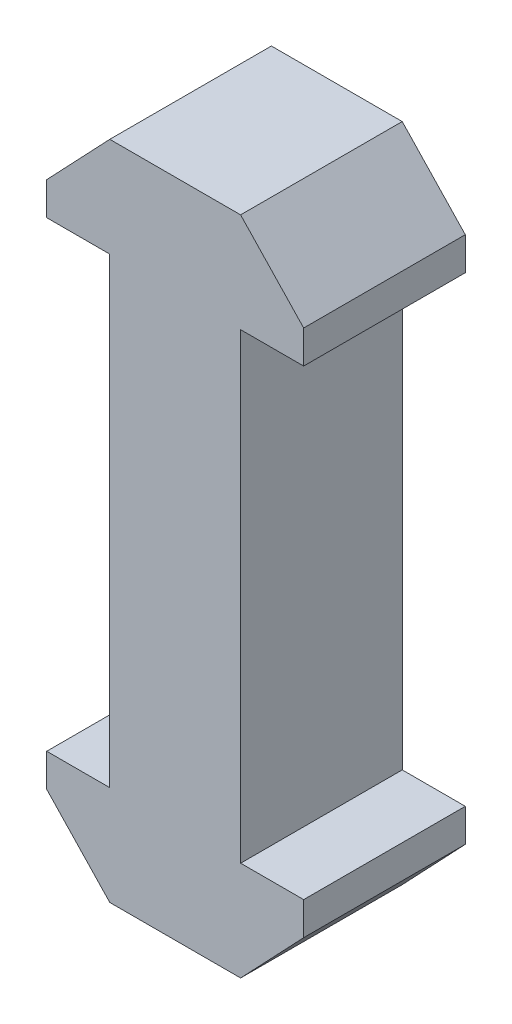
SolidWorks part; units mm, degrees
ref_plane "Front Plane" through (0, 0, 0) normal (0, 0, 1) x (1, 0, 0)
ref_plane "Top Plane" through (0, 0, 0) normal (0, 1, 0) x (1, 0, 0)
ref_plane "Right Plane" through (0, 0, 0) normal (1, 0, 0) x (0, 0, -1)
sketch "Sketch1" plane through (0, 0, 0) normal (0, 0, 1) x (1, 0, 0)
  line L3 (0, 0) -> (0, 14.2953) construction
  line L8 (0, 14.2953) -> (-8.6643, 14.2953) construction
  line L14 (-4.05, 0) -> (-4.05, 28.5906)
  line L15 (4.05, 0) -> (4.05, 28.5906)
  point P5 (-4.05, 14.2953)
  point P6 (4.05, 14.2953)
  line B0 (7.95, 0) -> (7.95, -2.04)
  line B1 (4.048, -6.1524) -> (-4.048, -6.1524)
  line B2 (-7.95, -2.04) -> (-7.95, 0)
  line B3 (-7.95, 0) -> (7.95, 0)
  line B4 (7.95, -2.04) -> (4.048, -6.1524)
  line B5 (-4.048, -6.1524) -> (-7.95, -2.04)
  line B6 (4.05, 0) -> (-4.05, 0) construction
  line B7 (7.95, 28.5906) -> (7.95, 30.6306)
  line B8 (4.048, 34.743) -> (-4.048, 34.743)
  line B9 (-7.95, 30.6306) -> (-7.95, 28.5906)
  line B10 (-7.95, 28.5906) -> (7.95, 28.5906)
  line B11 (7.95, 30.6306) -> (4.048, 34.743)
  line B12 (-4.048, 34.743) -> (-7.95, 30.6306)
  line B13 (4.05, 28.5906) -> (-4.05, 28.5906) construction
sketch_block_instance "Block1-1"
sketch_block "Block1" parameters "D1"=8.44, "D2"=2.6, "D3"=6, "D4"=16.7, "D6"=5.6686, "D7"=2.0404, "D8"=8.0963, "D9"=15.9, "D5"=2.4157
sketch_block_instance "Block1-5"
extrude "Boss-Extrude1" add sketch "Sketch1" along normal mid plane 10 contours B0 | B0 | B12 B9 B10 B7 B11 B8 | B10 L14 B3 L15 region at (0, -2.7416, 0) region at (0, 14.2953, 0) region at (0, 31.3322, 0)
